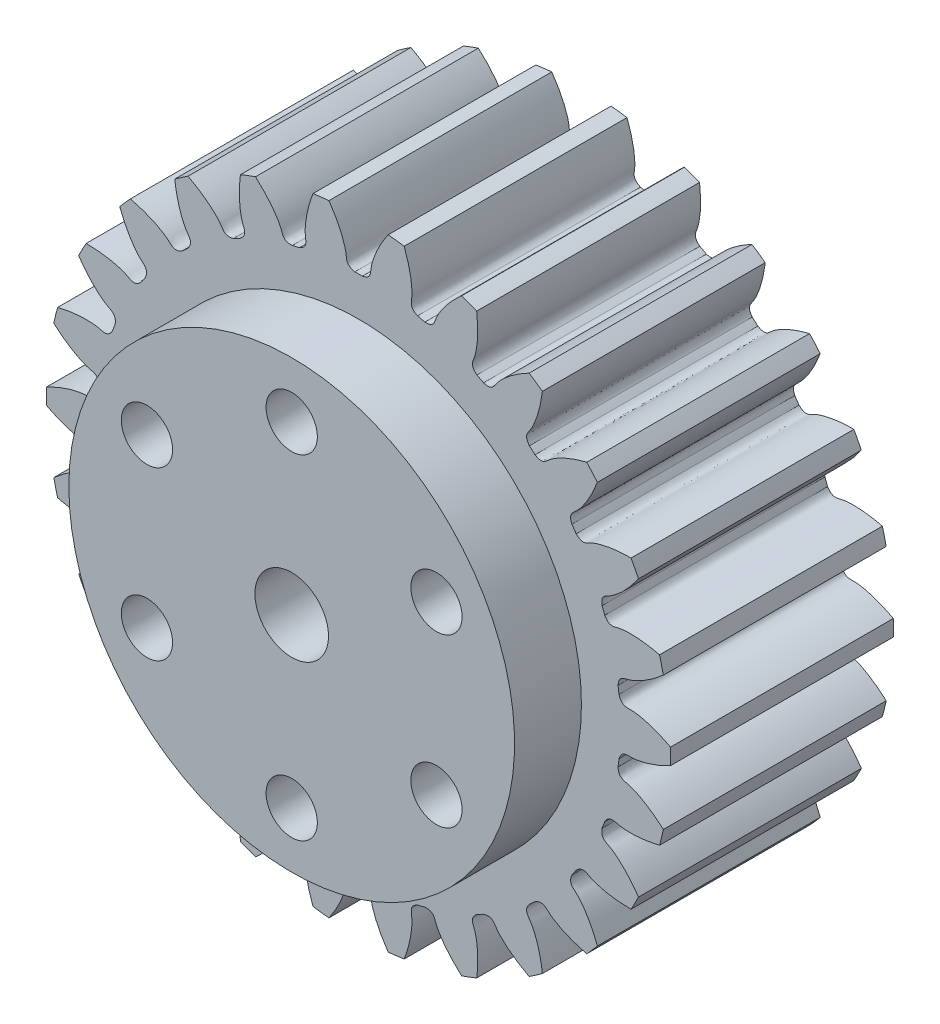
SolidWorks part; units mm, degrees
ref_plane "前视基准面" through (0, 0, 0) normal (0, 0, 1) x (1, 0, 0)
ref_plane "上视基准面" through (0, 0, 0) normal (0, 1, 0) x (1, 0, 0)
ref_plane "右视基准面" through (0, 0, 0) normal (1, 0, 0) x (0, 0, -1)
other "Configuration Table"
sketch "草图1" plane through (0, 0, 0) normal (0, 0, 1) x (1, 0, 0)
  circle A0 centre (0, 0) radius 14
  dimension "D1" = 28
extrude "凸台-拉伸1" add sketch "草图1" along normal blind 30
ref_axis "基准轴1" through (0, 0, 30) along (0, 0, -1)
sketch "草图2" plane through (0, 0, 0) normal (0, 0, 1) x (1, 0, 0)
  line L0 (0, 0) -> (0, 14) construction
  circle A0 centre (0, 0) radius 14 construction
  arc A1 (0.1671, 11.7488) -> (-0.1671, 11.7488) centre (0, 0) ccw
  arc A2 (3.2949, 15.9355) -> (-3.2949, 15.9355) centre (0, 0) ccw
  spline S0 degree 3 poles (0.1671, 11.7488) (0.5631, 11.8238) (0.5303, 12.0579) (0.5674, 12.2922) (0.573, 12.3235) (0.5801, 12.3594) (0.589, 12.4) (0.5999, 12.4451) (0.6129, 12.4947) (0.6282, 12.5488) (0.646, 12.6072) (0.6665, 12.6699) (0.6899, 12.7368) (0.7162, 12.8078) (0.7458, 12.8828) (0.7788, 12.9617) (0.8153, 13.0444) (0.8556, 13.1308) (0.8996, 13.2208) (0.9478, 13.3142) (1.0001, 13.4109) (1.0567, 13.5108) (1.1178, 13.6137) (1.1836, 13.7196) (1.2541, 13.8282) (1.3295, 13.9394) (1.4099, 14.0531) (1.4955, 14.1691) (1.5864, 14.2873) (1.6827, 14.4074) (1.7844, 14.5293) (1.8919, 14.6528) (2.005, 14.7778) (2.124, 14.9041) (2.2489, 15.0314) (2.3798, 15.1596) (2.5168, 15.2886) (2.6599, 15.418) (2.8094, 15.5478) (3.0195, 15.7231) (3.183, 15.8512) (3.2949, 15.9355) knots 0 0 0 0 0.122665 0.127715 0.133684 0.14057 0.148375 0.157098 0.166739 0.177298 0.188775 0.201171 0.214485 0.228717 0.243867 0.259935 0.276922 0.294827 0.31365 0.333391 0.35405 0.375628 0.398124 0.421538 0.44587 0.47112 0.497289 0.524375 0.55238 0.581303 0.611145 0.641904 0.673582 0.706178 0.739692 0.774124 0.809475 0.845743 0.88293 0.921035 1 1 1 1
  spline S1 degree 3 poles (-0.1671, 11.7488) (-0.5631, 11.8238) (-0.5303, 12.0579) (-0.5674, 12.2922) (-0.573, 12.3235) (-0.5801, 12.3594) (-0.589, 12.4) (-0.5999, 12.4451) (-0.6129, 12.4947) (-0.6282, 12.5488) (-0.646, 12.6072) (-0.6665, 12.6699) (-0.6899, 12.7368) (-0.7162, 12.8078) (-0.7458, 12.8828) (-0.7788, 12.9617) (-0.8153, 13.0444) (-0.8556, 13.1308) (-0.8996, 13.2208) (-0.9478, 13.3142) (-1.0001, 13.4109) (-1.0567, 13.5108) (-1.1178, 13.6137) (-1.1836, 13.7196) (-1.2541, 13.8282) (-1.3295, 13.9394) (-1.4099, 14.0531) (-1.4955, 14.1691) (-1.5864, 14.2873) (-1.6827, 14.4074) (-1.7844, 14.5293) (-1.8919, 14.6528) (-2.005, 14.7778) (-2.124, 14.9041) (-2.2489, 15.0314) (-2.3798, 15.1596) (-2.5168, 15.2886) (-2.6599, 15.418) (-2.8094, 15.5478) (-3.0195, 15.7231) (-3.183, 15.8512) (-3.2949, 15.9355) knots 0 0 0 0 0.122665 0.127715 0.133684 0.14057 0.148375 0.157098 0.166739 0.177298 0.188775 0.201171 0.214485 0.228717 0.243867 0.259935 0.276922 0.294827 0.31365 0.333391 0.35405 0.375628 0.398124 0.421538 0.44587 0.47112 0.497289 0.524375 0.55238 0.581303 0.611145 0.641904 0.673582 0.706178 0.739692 0.774124 0.809475 0.845743 0.88293 0.921035 1 1 1 1
extrude "切除-拉伸1" cut sketch "草图2" along normal through all
pattern_circular "阵列(圆周)1" count 26 every 13.846 about axis through (0, 0, 30) along (0, 0, -1) of "切除-拉伸1"
sketch "草图3" plane through (0, 0, 0) normal (0, 0, 1) x (1, 0, 0)
  circle A0 centre (0, 0) radius 13 construction
  dimension "Dn" = 26
sketch "草图4" plane through (0, 0, 30) normal (0, 0, 1) x (1, 0, 0)
  circle A0 centre (0, 0) radius 22.9861
extrude "切除-拉伸2" cut sketch "草图4" against normal offset from surface (20 mm away) 10 up to face at (0, 0, 0)
sketch "草图5" plane through (0, 0, 10) normal (0, 0, 1) x (1, 0, 0)
  circle A0 centre (0, 0) radius 1.65
  dimension "D1" = 3.3
sketch "草图6" plane through (0, 0, 0) normal (0, 0, -1) x (-1, 0, 0)
  circle A0 centre (0, 0) radius 10.75
  dimension "D1" = 21.5
extrude "Cut-Extrude1" cut sketch "草图5" against normal through all
sketch "Sketch1" plane through (0, 0, 10) normal (0, 0, 1) x (1, 0, 0)
  circle A2 centre (6.4952, 3.75) radius 1.15
  circle A7 centre (6.4952, -3.75) radius 1.15
  circle A10 centre (0, -7.5) radius 1.15
  circle A13 centre (-6.4952, -3.75) radius 1.15
  circle A16 centre (-6.4952, 3.75) radius 1.15
  circle A19 centre (0, 7.5) radius 1.15
  point P42 (0, 0)
  dimension "D1" = 2.3
  dimension "D2" = 2.3
  dimension "D3" = 2.3
  dimension "D4" = 2.3
  dimension "D5" = 2.3
  dimension "D6" = 2.3
extrude "Cut-Extrude2" cut sketch "Sketch1" against normal through all
sketch "Sketch2" plane through (0, 0, 10) normal (0, 0, 1) x (1, 0, 0)
  circle A0 centre (6.4952, 3.75) radius 2
  dimension "D1" = 4
sketch "Sketch3" plane through (0, 0, 10) normal (0, 0, -1) x (-1, 0, 0)
  circle A0 centre (0, 0) radius 10
  circle A1 centre (0, 7.5) radius 1.15 construction
  circle A2 centre (-6.4952, 3.75) radius 1.15 construction
  circle A3 centre (-6.4952, -3.75) radius 1.15 construction
  circle A4 centre (0, 0) radius 1.65 construction
  circle A5 centre (0, -7.5) radius 1.15 construction
  circle A6 centre (6.4952, 3.75) radius 1.15 construction
  circle A7 centre (6.4952, -3.75) radius 1.15 construction
  circle A8 centre (6.4952, -3.75) radius 1.15
  circle A9 centre (6.4952, 3.75) radius 1.15
  circle A10 centre (0, -7.5) radius 1.15
  circle A11 centre (0, 0) radius 1.65
  circle A12 centre (-6.4952, -3.75) radius 1.15
  circle A13 centre (-6.4952, 3.75) radius 1.15
  circle A14 centre (0, 7.5) radius 1.15
  dimension "D1" = 20
extrude "Boss-Extrude2" add sketch "Sketch3" against normal blind 3
sketch "Sketch4" plane through (0, 0, 0) normal (0, 0, -1) x (-1, 0, 0)
  circle A0 centre (0, 7.5) radius 2.25
  circle A1 centre (6.4952, 3.75) radius 2.25
  circle A2 centre (6.4952, -3.75) radius 2.25
  circle A3 centre (0, -7.5) radius 2.25
  circle A4 centre (-6.4952, -3.75) radius 2.25
  circle A5 centre (-6.4952, 3.75) radius 2.25
  point P16 (0, 0)
  dimension "D1" = 4.5
  dimension "D2" = 6
extrude "Cut-Extrude4" cut sketch "Sketch4" against normal offset from surface (10 mm away) 3 up to face at (-1.15, 7.5, 13)
